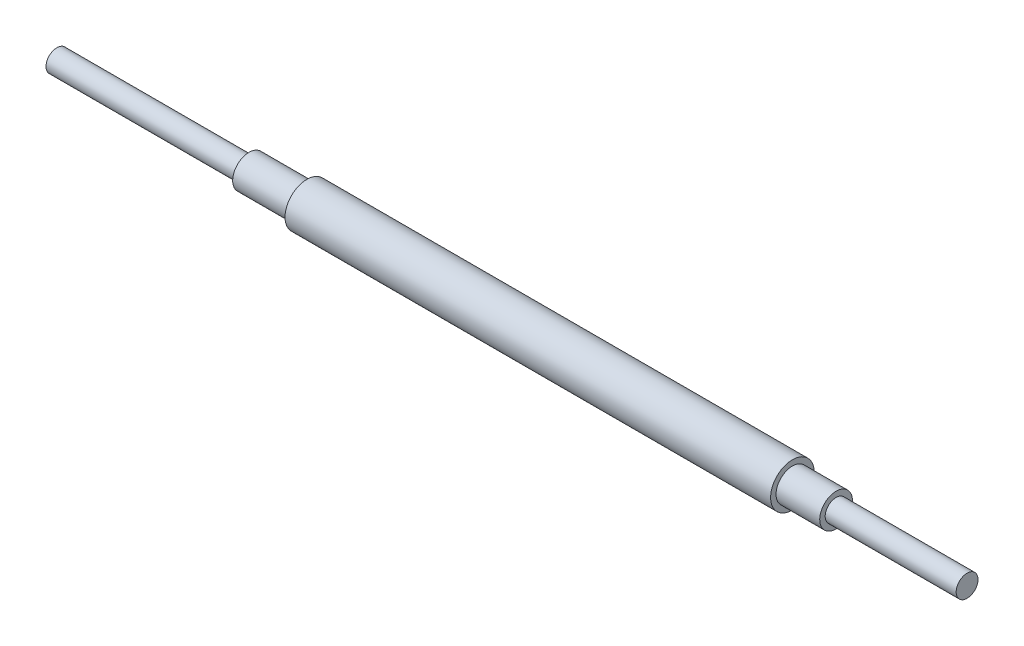
SolidWorks part; units mm, degrees
ref_plane "Front Plane" through (0, 0, 0) normal (0, 0, 1) x (1, 0, 0)
ref_plane "Top Plane" through (0, 0, 0) normal (0, 1, 0) x (1, 0, 0)
ref_plane "Right Plane" through (0, 0, 0) normal (1, 0, 0) x (0, 0, -1)
sketch "Sketch1" plane through (0, 0, 0) normal (0, 0, 1) x (1, 0, 0)
  line L3 (0.6124, 3.175) -> (0.6124, 0)
  line L4 (0.6124, 3.175) -> (-37.4876, 3.175)
  line L5 (-37.4876, 3.175) -> (-37.4876, 4.7625)
  line L6 (-37.4876, 4.7625) -> (-50.1876, 4.7625)
  line L7 (-50.1876, 4.7625) -> (-50.1876, 6.35)
  line L8 (-50.1876, 6.35) -> (-191.4116, 6.35)
  line L9 (-191.4116, 6.35) -> (-191.4116, 4.7625)
  line L10 (-191.4116, 4.7625) -> (-208.2309, 4.7625)
  line L11 (-208.2309, 4.7625) -> (-208.2309, 3.175)
  line L12 (-208.2309, 3.175) -> (-264.1109, 3.175)
  line L13 (-264.1109, 3.175) -> (-264.1109, 0)
  line L14 (-264.1109, 0) -> (0.6124, 0)
  line L16 (-191.4116, -5.0403) -> (-191.4116, 5.0403) construction
  line L18 (0, 0) -> (27.519, 0) construction
  line L19 (-259.0309, 10.16) -> (-259.0309, -10.16) construction
  point P1 (-202.2066, 4.7625)
  point P2 (-208.2309, 4.7625)
  dimension "D1" = 6.35
  dimension "D3" = 4.7625
  dimension "D4" = 3.175
  dimension ".35" = 38.1
  dimension "D6" = 3.175
  dimension "D7" = 141.224
  dimension "D9" = 5.08
  dimension "D2" = 12.7
revolve "Revolve1" add sketch "Sketch1" angle 360 about L14
equation "\"CompressorInnerDiameter\"=0.125"
equation "\"D4@Sketch1\"=\"CompressorInnerDiameter\""
